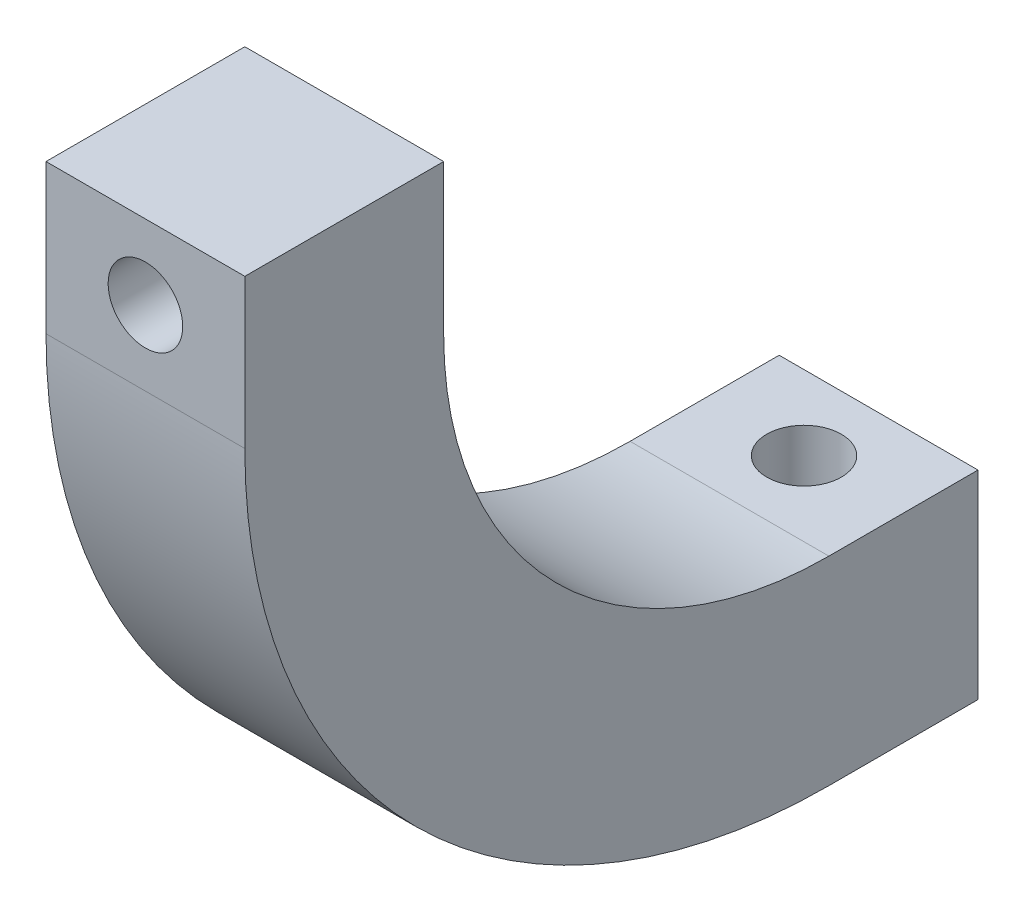
SolidWorks part; units mm, degrees
ref_plane "Front Plane" through (0, 0, 0) normal (0, 0, 1) x (1, 0, 0)
ref_plane "Top Plane" through (0, 0, 0) normal (0, 1, 0) x (1, 0, 0)
ref_plane "Right Plane" through (0, 0, 0) normal (1, 0, 0) x (0, 0, -1)
ref_axis "Z" through (0, 0, 22.75) along (0, 0, -1)
sketch "Sketch4" plane through (0, 0, 0) normal (0, 0, 1) x (1, 0, 0)
  circle A0 centre (0, 0) radius 17.5 construction
  dimension "D1" = 35
sketch "Sketch5" plane through (0, 0, 0) normal (1, 0, 0) x (0, 0, -1)
  line L0 (-18.5, 3) -> (-18.5, 0)
  line L1 (-18.5, 0) -> (-18.5, -3)
  line L2 (-26.5, -3) -> (-26.5, 3)
  line L6 (-26.5, 3) -> (-18.5, 3)
  line L12 (-22.75, 0) -> (-13.0351, 0) construction
  line L13 (0, 0) -> (-14.9091, -14.9091) construction
  line L14 (0, 0) -> (7.0065, 0) construction
  line L15 (0, -18.5) -> (-3, -18.5)
  line L16 (3, -18.5) -> (0, -18.5)
  line L17 (-3, -26.5) -> (3, -26.5)
  line L18 (3, -26.5) -> (3, -18.5)
  circle A0 centre (0, 0) radius 14 construction
  arc A1 (-18.5, -3) -> (-3, -18.5) centre (-3, -3) ccw
  arc A2 (-26.5, -3) -> (-3, -26.5) centre (-3, -3) ccw
  point P2 (9.4307, -21)
  point P4 (0, -2.1363)
  point P20 (-20.5214, -4.6985)
  point P22 (-36.7289, 3)
  dimension "D1" = 28
  dimension "D4" = 3
  dimension "D2" = 45
  dimension "D3" = 8
  dimension "D5" = 18.5
sketch "Sketch6" plane through (0, 0, 0) normal (0, 1, 0) x (1, 0, 0)
  circle A0 centre (0, 0) radius 17.5 construction
  dimension "D1" = 35
extrude "Boss-Extrude1" add sketch "Sketch5" along normal blind 4 and the other way blind 4
sketch "Sketch7" plane through (0, 0, 0) normal (0, 0, 1) x (1, 0, 0)
  circle A0 centre (0, 0) radius 1.5
  dimension "D1" = 3
extrude "Cut-Extrude1" cut sketch "Sketch7" along normal through all
sketch "Sketch8" plane through (0, 0, 0) normal (0, 1, 0) x (1, 0, 0)
  circle A0 centre (0, 0) radius 1.5
  dimension "D1" = 3
extrude "Cut-Extrude2" cut sketch "Sketch8" against normal through all
ref_axis "Y" through (0, -9.3489, 0) along (0, -1, 0)
equation "\"rbracket-width\"= \"L2Thickness\""
equation "\"EyeCaptureRadius\"= ( \"EyeDiameter\" + \"EyeClearance\" ) / 2"
equation "\"rbracket_planetocenterline_dist\"= \"BasePlaneDistance\""
equation "\"EyeDiameter\" = 35"
equation "\"BasePlaneDistance\" = \"EyeDiameter\"/2+19.84"
equation "\"EyeClearance\" = 2"
equation "\"D1@Sketch4\"=\"EyeDiameter\""
equation "\"D1@Sketch6\"=\"EyeDiameter\""
equation "\"D1@Boss-Extrude1\"=\"rbracket-width\"/2"
equation "\"D2@Boss-Extrude1\"=\"rbracket-width\"/2"
equation "\"L2Thickness\" = 8"
equation "\"D3@Sketch5\"=\"L2Thickness\""
equation "\"D5@Sketch5\"=(\"EyeDiameter\"+\"EyeClearance\")/2"
